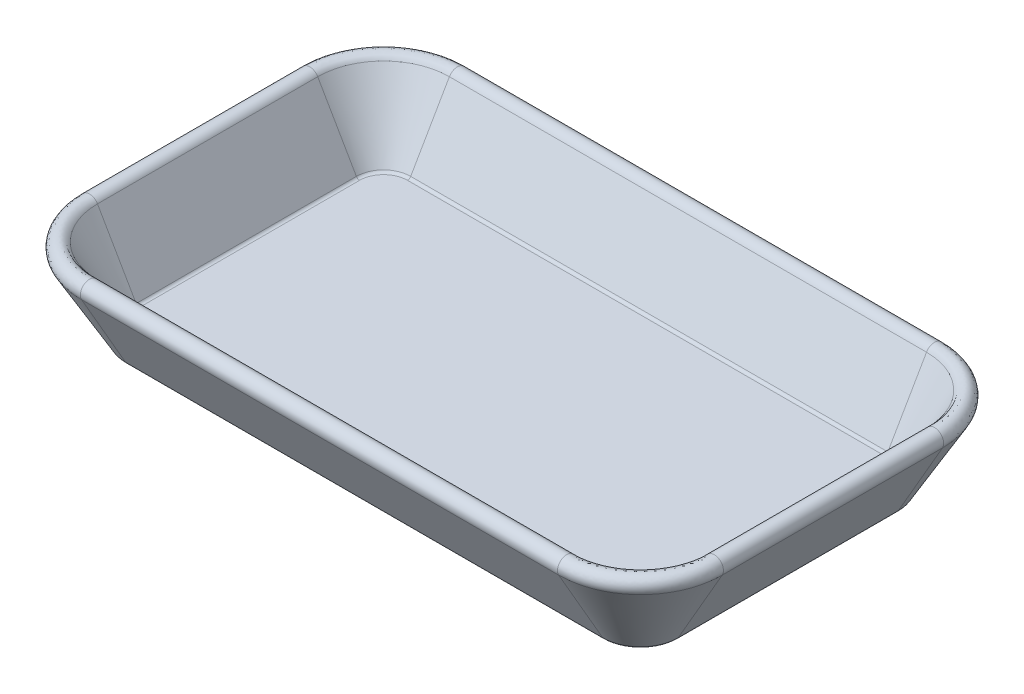
SolidWorks part; units mm, degrees
ref_plane "Front Plane" through (0, 0, 0) normal (0, 0, 1) x (1, 0, 0)
ref_plane "Top Plane" through (0, 0, 0) normal (0, 1, 0) x (1, 0, 0)
ref_plane "Right Plane" through (0, 0, 0) normal (1, 0, 0) x (0, 0, -1)
sketch "Sketch1" plane through (0, 0, 0) normal (0, 1, 0) x (1, 0, 0)
  line L1 (-65, -40) -> (65, -40)
  line L2 (-75, -30) -> (-75, 30)
  line L3 (-65, 40) -> (65, 40)
  line L4 (75, -30) -> (75, 30)
  line L5 (-75, -40) -> (75, 40) construction
  line L6 (-75, 40) -> (75, -40) construction
  arc A0 (65, 40) -> (75, 30) centre (65, 30) cw
  arc A1 (65, -40) -> (75, -30) centre (65, -30) ccw
  arc A2 (-65, -40) -> (-75, -30) centre (-65, -30) cw
  arc A3 (-75, 30) -> (-65, 40) centre (-65, 30) cw
  point P0 (0, 0)
  dimension "D3" = 10
  dimension "D1" = 150
  dimension "D2" = 80
extrude "Boss-Extrude1" add sketch "Sketch1" along normal blind 25 draft 30 draft outward yes
shell "Shell1" thickness 5 removed face at (0, 25, 0)
fillet "Fillet1" radius 1 8 edges at (-70.0298, 5, 35.0298) (-72.1132, 5, 0) (-70.0298, 5, -35.0298) (0, 5, -37.1132) (70.0298, 5, -35.0298) (72.1132, 5, 0) (70.0298, 5, 35.0298) (0, 5, 37.1132)
fillet "Fillet2" 2 edges at (83.6603, 25, 0) (89.4338, 25, 0) type full round first side face at (78.0311, 15.25, 0) second side face at (82.2169, 12.5, 0) middle face at (0, 25, 0)
fillet "Fillet3" radius 1 8 edges at (-72.0711, 0, 37.0711) (-75, 0, 0) (-72.0711, 0, -37.0711) (0, 0, -40) (72.0711, 0, -37.0711) (75, 0, 0) (72.0711, 0, 37.0711) (0, 0, 40)
